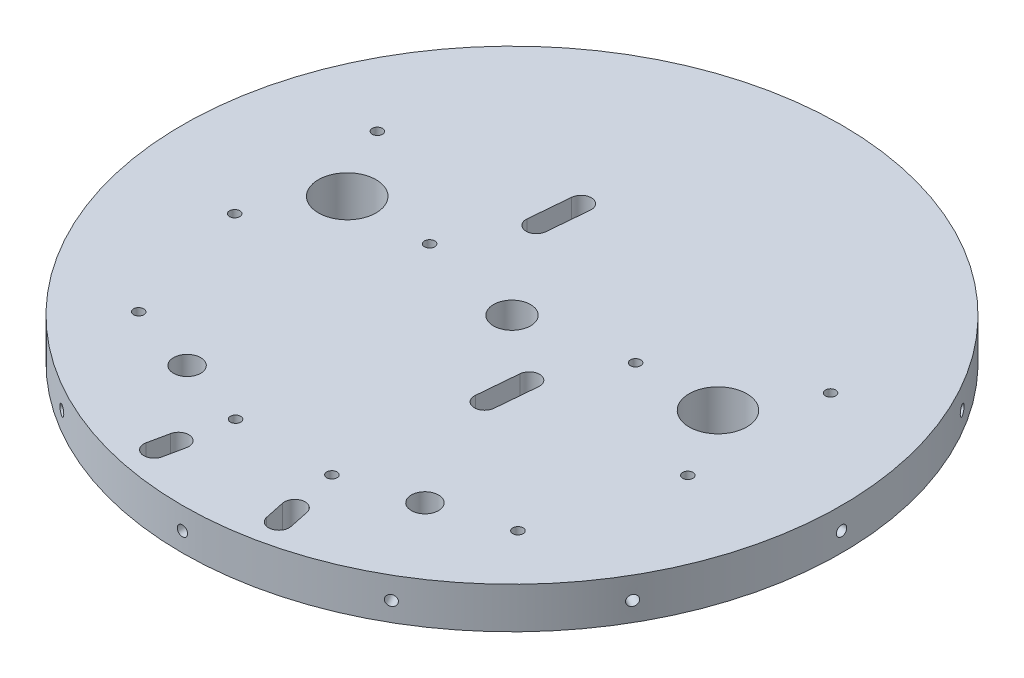
SolidWorks part; units mm, degrees
material "6061 Alloy"
ref_plane "Front Plane" through (0, 0, 0) normal (0, 0, 1) x (1, 0, 0)
ref_plane "Top Plane" through (0, 0, 0) normal (0, 1, 0) x (1, 0, 0)
ref_plane "Right Plane" through (0, 0, 0) normal (1, 0, 0) x (0, 0, -1)
sketch "Sketch1" plane through (0, 0, 0) normal (0, 1, 0) x (1, 0, 0)
  circle A0 centre (0, 0) radius 80
extrude "Boss-Extrude1" add sketch "Sketch1" against normal blind 10
sketch "Sketch3" plane through (0, 0, 0) normal (0, 1, 0) x (1, 0, 0)
  circle A0 centre (0, 0) radius 4.5
extrude "Cut-Extrude1" cut sketch "Sketch3" against normal blind 12
sketch "Sketch4" plane through (0, 0, 0) normal (0, 1, 0) x (1, 0, 0)
  line L1 (45, 5) -> (-45, 5)
  circle A2 centre (-45, 5) radius 7
  circle A3 centre (45, 5) radius 7
  point P5 (0, 0)
extrude "Cut-Extrude2" cut sketch "Sketch4" against normal blind 12 contours A2 | A3 region at (-51.802, 0, -5) region at (45, 0, -11.802)
ref_plane "Plane1" through (0, 0, 80) normal (0, 0, 1) x (1, 0, 0)
sketch "Sketch5" plane through (0, 0, 80) normal (0, 0, 1) x (1, 0, 0)
  circle A0 centre (0, -5.3239) radius 1.25
extrude "Cut-Extrude3" cut sketch "Sketch5" against normal blind 15
pattern_circular "CirPattern1" count 12 over 360 about axis through (0, 0, 0) along (0, 1, 0) of "Cut-Extrude3"
sketch "Sketch6" plane through (0, 0, 0) normal (0, 1, 0) x (1, 0, 0)
  line L2 (-45, 5) -> (-25, 5) construction
  line L3 (45, 5) -> (25, 5) construction
  circle A2 centre (-25, 5) radius 1.25
  circle A3 centre (25, 5) radius 1.25
  circle A4 centre (-55, 22.3205) radius 1.25
  circle A5 centre (-55, -12.3205) radius 1.25
  circle A6 centre (55, 22.3205) radius 1.25
  circle A7 centre (55, -12.3205) radius 1.25
  point P7 (-45, 5)
  point P18 (45, 5)
  dimension "D1" = 3
  dimension "D2" = 3
extrude "Cut-Extrude4" cut sketch "Sketch6" against normal up to next contours A2 | A3 | A4 | A5 | A7 | A6 region at (-25, 0, -5) region at (25, 0, -5) region at (-55, 0, -22.3205) region at (-55, 0, 12.3205) region at (55, 0, -22.3205) region at (55, 0, 12.3205)
sketch "Sketch9" plane through (0, -10, 0) normal (0, -1, 0) x (1, 0, 0)
  circle A0 centre (0, 0) radius 12.5
extrude "Cut-Extrude5" cut sketch "Sketch9" against normal blind 3
sketch "Sketch10" plane through (0, 0, 0) normal (0, 1, 0) x (1, 0, 0)
  line L0 (0, 0) -> (0, -80) construction
  line L1 (0, 0) -> (28.8675, -50)
  line L2 (0, 0) -> (-28.8675, -50)
  line L4 (-28.8675, -50) -> (28.8675, -50)
  circle A0 centre (0, 0) radius 80 construction
  circle A4 centre (-28.8675, -50) radius 3.3
  circle A5 centre (28.8675, -50) radius 3.3
  point P12 (17.3205, -60)
  dimension "D1" = 30
  dimension "D2" = 30
extrude "Cut-Extrude6" cut sketch "Sketch10" against normal up to next contours L1 A5 L4 | L4 A5 L1 | A4 region at (29.2314, 0, 50.2101) region at (27.0481, 0, 48.9496)
sketch "Sketch11" plane through (0, 0, 0) normal (0, 1, 0) x (1, 0, 0)
  line L0 (0, 0) -> (0, -80) construction
  line L1 (28.8675, -50) -> (0, -59.1019) construction
  line L2 (0, -59.1019) -> (-28.8675, -50) construction
  circle A0 centre (0, 0) radius 80 construction
  circle A1 centre (11.7006, -55.4127) radius 1.25
  circle A2 centre (-11.7006, -55.4127) radius 1.25
  circle A3 centre (46.0344, -44.5873) radius 1.25
  circle A4 centre (-46.0344, -44.5873) radius 1.25
  point P20 (28.8675, -50)
  point P22 (-28.8675, -50)
  dimension "D2" = 18
  dimension "D3" = 18
  dimension "D1" = 145
  dimension "D4" = 2
  dimension "D5" = 2
extrude "Cut-Extrude7" cut sketch "Sketch11" against normal up to next
sketch "Sketch12" plane through (0, 0, 0) normal (0, 1, 0) x (1, 0, 0)
  line L0 (0, 0) -> (11.7006, -55.4127) construction
  line L1 (11.7006, -55.4127) -> (16.5279, -78.2741) construction
  line L2 (0, 0) -> (-11.7006, -55.4127) construction
  line L3 (-11.7006, -55.4127) -> (-16.5279, -78.2741) construction
  line L4 (16.5603, -66.3269) -> (17.5933, -71.219)
  line L5 (12.7012, -72.252) -> (11.6682, -67.3599)
  line L6 (-11.6682, -67.3599) -> (-12.7012, -72.252)
  line L7 (-16.5603, -66.3269) -> (-17.5933, -71.219)
  circle A0 centre (0, 0) radius 80 construction
  arc A1 (16.5603, -66.3269) -> (11.6682, -67.3599) centre (14.1142, -66.8434) ccw
  arc A2 (-11.6682, -67.3599) -> (-16.5603, -66.3269) centre (-14.1142, -66.8434) ccw
  arc A3 (-17.5933, -71.219) -> (-12.7012, -72.252) centre (-15.1472, -71.7355) ccw
  arc A4 (12.7012, -72.252) -> (17.5933, -71.219) centre (15.1472, -71.7355) ccw
  dimension "D1" = 5
  dimension "D2" = 5
extrude "Cut-Extrude8" cut sketch "Sketch12" against normal up to next
sketch "Sketch13" plane through (0, 0, 0) normal (0, 1, 0) x (1, 0, 0)
  line L0 (28.8675, -50) -> (0, 0) construction
  line L1 (0, 0) -> (-40, 69.282) construction
  line L2 (33.1976, -47.5) -> (4.3301, 2.5) construction
  line L3 (18.0385, -14.28) -> (17.6027, -19.2609)
  line L4 (13.0575, -13.8442) -> (12.6218, -18.8252)
  line L5 (-17.8099, 0.4442) -> (-13.1901, 53.2494) construction
  line L6 (9.2515, -86.0316) -> (21.4088, 52.9265) construction
  line L7 (-12.7916, 29.1194) -> (-13.2274, 24.1384)
  line L8 (-17.7726, 29.5552) -> (-18.2084, 24.5742)
  line L9 (-12.5737, 31.6099) -> (-13.4453, 21.6479)
  line L10 (-17.5547, 32.0457) -> (-18.4263, 22.0837)
  line L11 (18.2564, -11.7895) -> (17.3848, -21.7514)
  line L12 (13.2754, -11.3537) -> (12.4039, -21.3156)
  circle A0 centre (0, 0) radius 80 construction
  arc A11 (-12.5737, 31.6099) -> (-17.5547, 32.0457) centre (-15.0642, 31.8278) ccw
  arc A12 (-18.4263, 22.0837) -> (-13.4453, 21.6479) centre (-15.9358, 21.8658) ccw
  arc A14 (18.2564, -11.7895) -> (13.2754, -11.3537) centre (15.7659, -11.5716) ccw
  arc A15 (-13.4521, 23.2998) -> (-13.2274, 24.1384) centre (-15.7179, 24.3563) ccw
  arc A16 (12.4039, -21.3156) -> (17.3848, -21.7514) centre (14.8943, -21.5335) ccw
  point P16 (-15.5, 26.8468)
  point P19 (15.3301, -16.5526)
  point P22 (-15.5, 26.8468)
  point P25 (15.3301, -16.5526)
  point P26 (15.3301, -16.5526)
  dimension "D2" = 35
  dimension "D3" = 35
  dimension "D1" = 5
extrude "Cut-Extrude10" cut sketch "Sketch13" against normal up to next contours L10 A12 L9 L7 A11 L8 | L12 A16 L11 L3 A14 L4 region at (15.3301, 0, 16.5526) region at (-15.5, 0, -26.8468)
